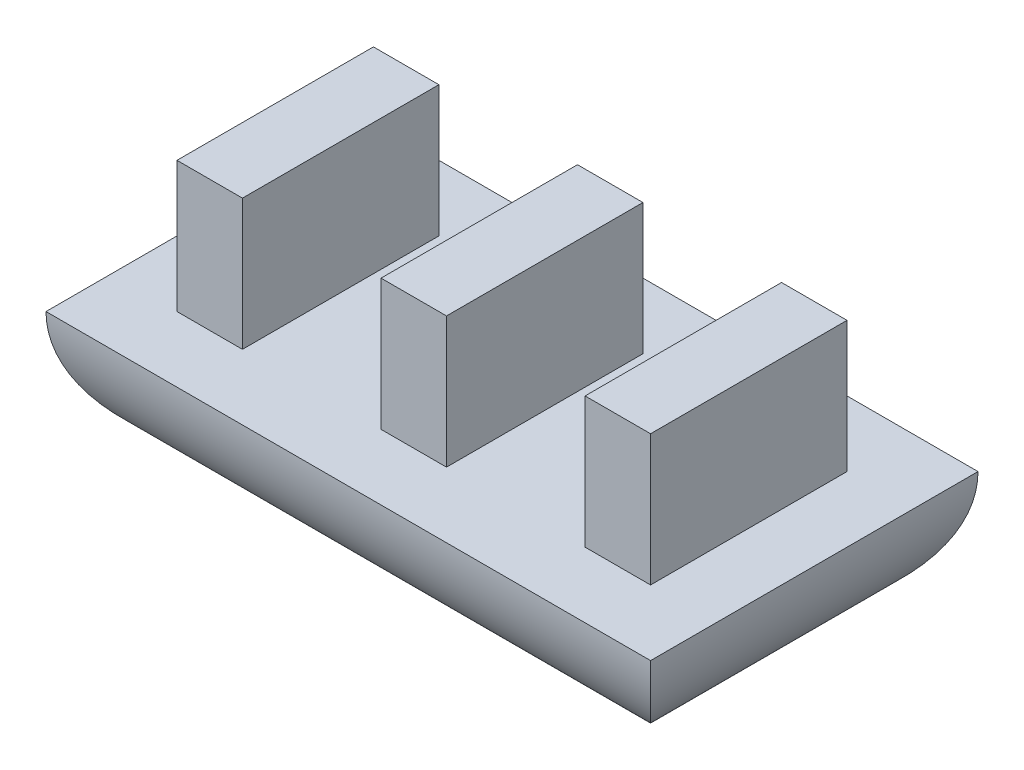
SolidWorks part; units mm, degrees
material "Silicon"
ref_plane "Front Plane" through (0, 0, 0) normal (0, 0, 1) x (1, 0, 0)
ref_plane "Top Plane" through (0, 0, 0) normal (0, 1, 0) x (1, 0, 0)
ref_plane "Right Plane" through (0, 0, 0) normal (1, 0, 0) x (0, 0, -1)
sketch "Sketch1" plane through (0, 0, 0) normal (0, 1, 0) x (1, 0, 0)
  line L0 (0, 3.9688) -> (14.6558, 3.9688) construction
  line L1 (0, 0) -> (14.6558, 0)
  line L2 (0, 0) -> (0, 7.9375)
  line L3 (0, 7.9375) -> (14.6558, 7.9375)
  line L4 (14.6558, 0) -> (14.6558, 7.9375)
  line L6 (1.5875, 1.5875) -> (3.175, 1.5875)
  line L7 (1.5875, 1.5875) -> (1.5875, 6.35)
  line L8 (1.5875, 6.35) -> (3.175, 6.35)
  line L9 (3.175, 1.5875) -> (3.175, 6.35)
  line L10 (1.5875, 1.5875) -> (3.175, 6.35) construction
  line L11 (1.5875, 6.35) -> (3.175, 1.5875) construction
  line L12 (6.5341, 1.5875) -> (8.1216, 1.5875)
  line L13 (6.5341, 1.5875) -> (6.5341, 6.35)
  line L14 (6.5341, 6.35) -> (8.1216, 6.35)
  line L15 (8.1216, 1.5875) -> (8.1216, 6.35)
  line L16 (6.5341, 1.5875) -> (8.1216, 6.35) construction
  line L17 (6.5341, 6.35) -> (8.1216, 1.5875) construction
  line L18 (11.4808, 1.5875) -> (13.0683, 1.5875)
  line L19 (11.4808, 1.5875) -> (11.4808, 6.35)
  line L20 (11.4808, 6.35) -> (13.0683, 6.35)
  line L21 (13.0683, 1.5875) -> (13.0683, 6.35)
  line L22 (11.4808, 1.5875) -> (13.0683, 6.35) construction
  line L23 (11.4808, 6.35) -> (13.0683, 1.5875) construction
  point P7 (2.3813, 3.9688)
  point P12 (7.3279, 3.9688)
  point P17 (12.2745, 3.9688)
  dimension "D1" = 1.5875
  dimension "D2" = 1.5875
  dimension "D3" = 14.6558
  dimension "D4" = 1.5875
  dimension "D5" = 7.9375
  dimension "D6" = 4.7625
extrude "Boss-Extrude1" add sketch "Sketch1" against normal blind 3.175 contours L1 L4 L3 L2 L21 L18 L19 L20 L15 L12 L13 L14 L9 L6 L7 L8 | L6 L9 L8 L7 | L12 L15 L14 L13 | L18 L21 L20 L19 region at (0.1667, 0, -3.9688) region at (2.3812, 0, -3.9687) region at (7.3279, 0, -3.9688) region at (12.2745, 0, -3.9687)
extrude "Boss-Extrude2" add sketch "Sketch1<3>" along normal blind 3.175 contours L6 L9 L8 L7 | L12 L15 L14 L13 | L18 L21 L20 L19 region at (2.3812, 0, -3.9687) region at (7.3279, 0, -3.9688) region at (12.2745, 0, -3.9687)
sketch "Sketch1<3>" plane through (0, 0, 0) normal (0, 1, 0) x (1, 0, 0) same geometry as "Sketch1"
fillet "Fillet1" radius 3.175 4 edges at (14.6558, -3.175, -3.9688) (7.3279, -3.175, -7.9375) (0, -3.175, -3.9688) (7.3279, -3.175, 0)
